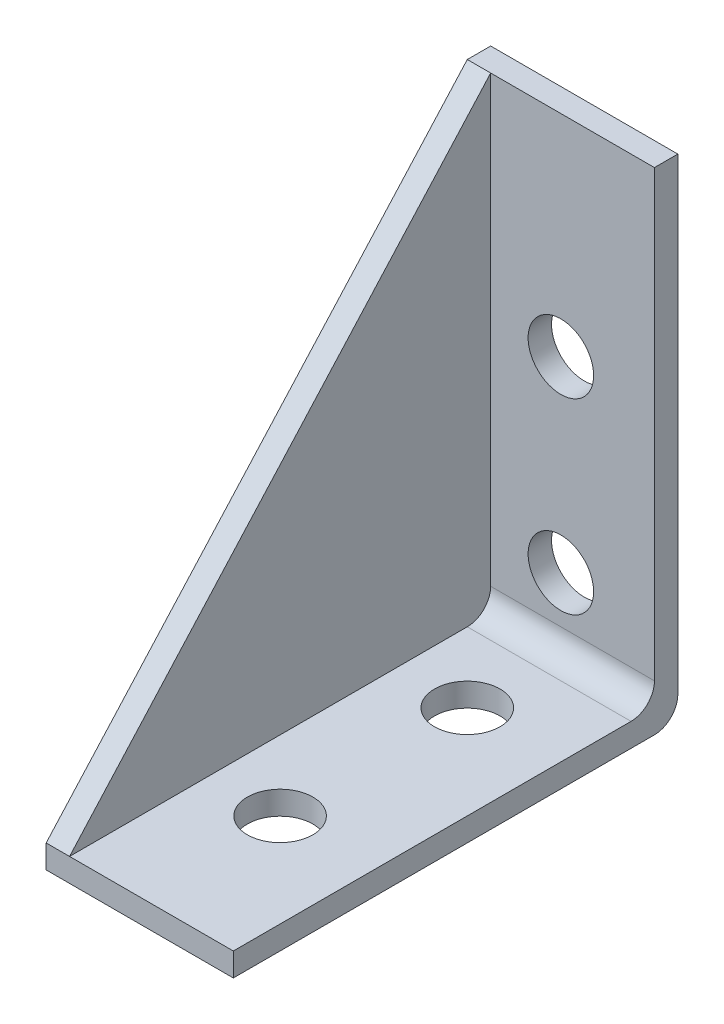
SolidWorks part; units mm, degrees
ref_plane "Alzado" through (0, 0, 0) normal (0, 0, 1) x (1, 0, 0)
ref_plane "Planta" through (0, 0, 0) normal (0, 1, 0) x (1, 0, 0)
ref_plane "Vista lateral" through (0, 0, 0) normal (1, 0, 0) x (0, 0, -1)
sketch "Croquis1" plane through (0, 0, 0) normal (0, 0, 1) x (1, 0, 0)
  line L1 (0, 0) -> (40, 0)
  line L2 (0, 0) -> (0, 105)
  line L3 (0, 105) -> (40, 105)
  line L4 (40, 0) -> (40, 105)
  dimension "D1" = 40
  dimension "D2" = 105
extrude "Saliente-Extruir1" add sketch "Croquis1" along normal blind 5 contours L3 L4 L1 L2
sketch "Croquis2" plane through (0, 0, 5) normal (0, 0, 1) x (1, 0, 0)
  line L0 (0, 0) -> (40, 0) construction
  line L1 (0, 0) -> (0, 105) construction
  circle A0 centre (20, 20) radius 7
  circle A1 centre (20, 60) radius 7
  dimension "D1" = 20
  dimension "D2" = 40
  dimension "D3" = 20
  dimension "D4" = 20
extrude "Cortar-Extruir1" cut sketch "Croquis2" against normal blind 5 contours A1
extrude "Cortar-Extruir2" cut sketch "Croquis2<3>" against normal blind 5 contours A0
sketch "Croquis2<3>" plane through (0, 0, 5) normal (0, 0, 1) x (1, 0, 0) same geometry as "Croquis2"
sketch "Croquis4" plane through (0, 0, 5) normal (0, 0, 1) x (1, 0, 0)
  line L0 (0, 0) -> (0, 5)
  line L1 (0, 0) -> (0, 105) construction
  line L2 (0, 5) -> (40, 5)
  line L3 (40, 0) -> (40, 105) construction
  line L4 (40, 5) -> (40, 0)
  line L5 (40, 0) -> (0, 0)
  dimension "D1" = 5
  dimension "D2" = 40
extrude "Saliente-Extruir2" add sketch "Croquis4" along normal blind 90
sketch "Croquis5" plane through (0, 5, 0) normal (0, 1, 0) x (1, 0, 0)
  line L0 (13, -5) -> (27, -5) construction
  circle A0 centre (20, -25) radius 7
  circle A1 centre (20, -65) radius 7
  dimension "D1" = 20
  dimension "D2" = 40
extrude "Cortar-Extruir3" cut sketch "Croquis5" against normal blind 90 contours A0
extrude "Cortar-Extruir4" cut sketch "Croquis5<3>" against normal blind 90
sketch "Croquis5<3>" plane through (0, 5, 0) normal (0, 1, 0) x (1, 0, 0) same geometry as "Croquis5"
fillet "Redondeo3" radius 5 1 edges at (20, 5, 5)
fillet "Redondeo4" radius 5 1 edges at (20, 0, 0)
sketch "Croquis6" plane through (0, 0, 0) normal (-1, 0, 0) x (0, 0, 1)
  line L0 (5, 105) -> (95, 5)
  line L1 (95, 5) -> (10, 5)
  line L2 (5, 105) -> (5, 10)
  arc A0 (5, 10) -> (10, 5) centre (10, 10) ccw
extrude "Saliente-Extruir3" add sketch "Croquis6" against normal blind 5
